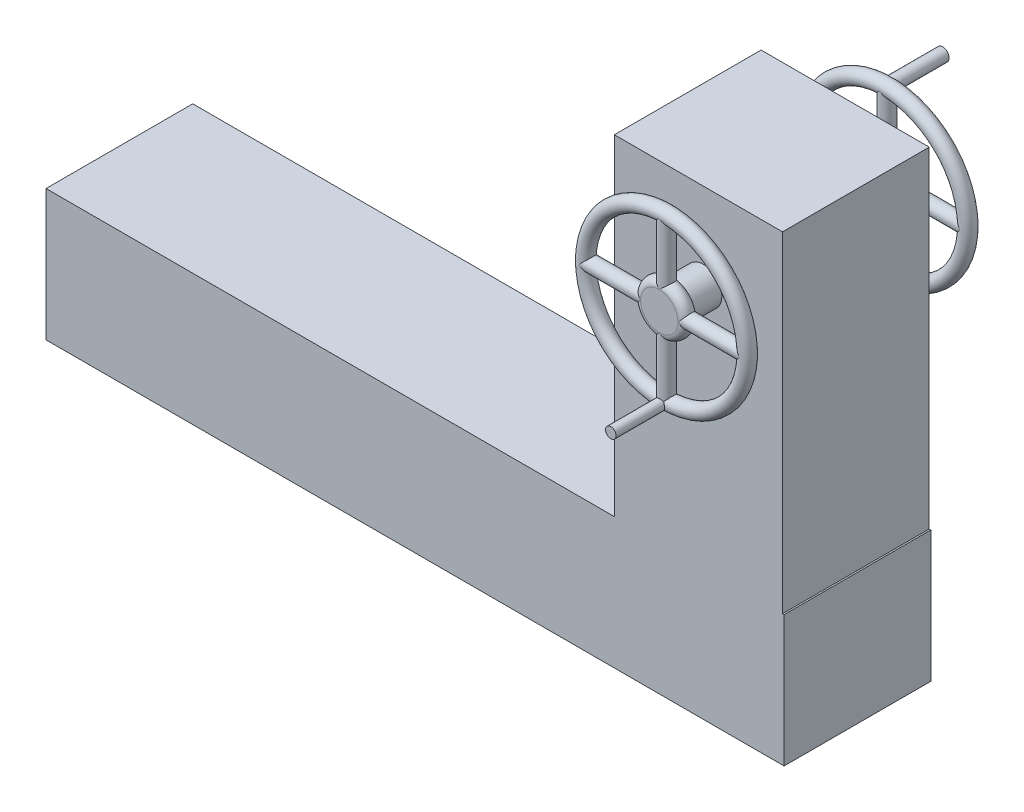
SolidWorks part; units mm, degrees
ref_plane "Front Plane" through (0, 0, 0) normal (0, 0, 1) x (1, 0, 0)
ref_plane "Top Plane" through (0, 0, 0) normal (0, 1, 0) x (1, 0, 0)
ref_plane "Right Plane" through (0, 0, 0) normal (1, 0, 0) x (0, 0, -1)
sketch "Sketch3" plane through (8230.2525, 0, 0) normal (1, 0, 0) x (0, 0, -1)
  line L1 (-757.4176, 4972.7823) -> (651.0552, 4972.7823)
  line L2 (-757.4176, 4972.7823) -> (-757.4176, 3619.5437)
  line L3 (-757.4176, 3619.5437) -> (651.0552, 3619.5437)
  line L4 (651.0552, 4972.7823) -> (651.0552, 3619.5437)
extrude "Boss-Extrude1" add sketch "Sketch3" along normal blind 7620
sketch "Sketch4" plane through (0, 4972.7823, 0) normal (0, 1, 0) x (1, 0, 0)
  line L0 (15850.2525, 651.0552) -> (8230.2525, 651.0552) construction
  line L1 (14097.8506, 651.0552) -> (15834.0285, 651.0552)
  line L2 (14097.8506, 651.0552) -> (14097.8506, -757.4176)
  line L3 (14097.8506, -757.4176) -> (15834.0285, -757.4176)
  line L4 (15834.0285, 651.0552) -> (15834.0285, -757.4176)
  line L5 (15850.2525, -757.4176) -> (8230.2525, -757.4176) construction
extrude "Boss-Extrude2" add sketch "Sketch4" along normal blind 3414.522
sketch "Sketch5" plane through (0, 0, 757.4176) normal (0, 0, 1) x (1, 0, 0)
  circle A0 centre (15017.2611, 7497.9493) radius 190.5
  dimension "D1" = 381
extrude "Boss-Extrude3" add sketch "Sketch5" along normal blind 381
sketch "Sketch8" plane through (0, 0, 1138.4176) normal (0, 0, 1) x (1, 0, 0)
  line L0 (15017.2611, 7497.9493) -> (15017.2611, 8331.052) construction
ref_plane "Plane1" through (15017.2611, 0, 0) normal (1, 0, 0) x (0, 0, -1)
sketch "Sketch9" plane through (15017.2611, 0, 0) normal (1, 0, 0) x (0, 0, -1)
  line L0 (-1138.4176, 7497.9493) -> (-1138.4176, 8331.052) construction
  line L1 (-1138.4176, 7497.9493) -> (-1557.7955, 7497.9493) construction
  circle A0 centre (-1138.4176, 8331.052) radius 75
  dimension "D1" = 150
revolve "Revolve3" add sketch "Sketch9" angle 360 about L1
sketch "Sketch10" plane through (15017.2611, 0, 0) normal (1, 0, 0) x (0, 0, -1)
  line L0 (-1138.4176, 7690.5571) -> (-1138.4176, 7497.7009) construction
  line L1 (-1138.4176, 7497.9493) -> (-1138.4176, 8331.052) construction
  line L2 (-1063.6879, 7690.5571) -> (-1063.6879, 7497.7009)
  line L3 (-1213.1473, 7690.5571) -> (-1213.1473, 7497.7009)
  line L4 (-1213.1473, 7497.7009) -> (-1063.6879, 7497.7009) construction
  line L5 (-1213.1473, 7497.7009) -> (-1063.6879, 7497.7009)
  arc A0 (-1063.6879, 7690.5571) -> (-1213.1473, 7690.5571) centre (-1138.4176, 7690.5571) ccw
revolve "Revolve5" add sketch "Sketch10" angle 360 about L5
sketch "Sketch11" plane through (15017.2611, 0, 0) normal (1, 0, 0) x (0, 0, -1)
  line L0 (-1138.4176, 7497.9493) -> (-1138.4176, 8331.052) construction
  circle A0 centre (-1138.4176, 7497.9493) radius 74.5
  dimension "D1" = 149
extrude "Boss-Extrude4" add sketch "Sketch11" along normal up to surface and the other way up to surface
ref_plane "Plane2" through (0, 8331.052, 0) normal (0, 1, 0) x (1, 0, 0)
sketch "Sketch12" plane through (0, 8331.052, 0) normal (0, 1, 0) x (1, 0, 0)
  circle A0 centre (15017.2611, -1138.4176) radius 74.5
  dimension "D1" = 149
extrude "Boss-Extrude5" add sketch "Sketch12" against normal blind 1640
mirror "Mirror2" about plane through (0, 0, 0) normal (0, 0, 1) of bodies 107
sketch "Sketch13" plane through (0, 0, 1213.1473) normal (0, 0, 1) x (1, 0, 0)
  circle A0 centre (15017.2611, 6661.246) radius 54.4286
extrude "Boss-Extrude6" add sketch "Sketch13" along normal blind 500 and the other way up to surface
sketch "Sketch14" plane through (0, 0, -1213.1473) normal (0, 0, -1) x (-1, 0, 0)
  circle A0 centre (-15017.2611, 8331.052) radius 66.2061
extrude "Boss-Extrude7" add sketch "Sketch14" along normal blind 500 and the other way up to surface
scale "Scale1" scale about origin uniform scaling yes scale factor 0.1
